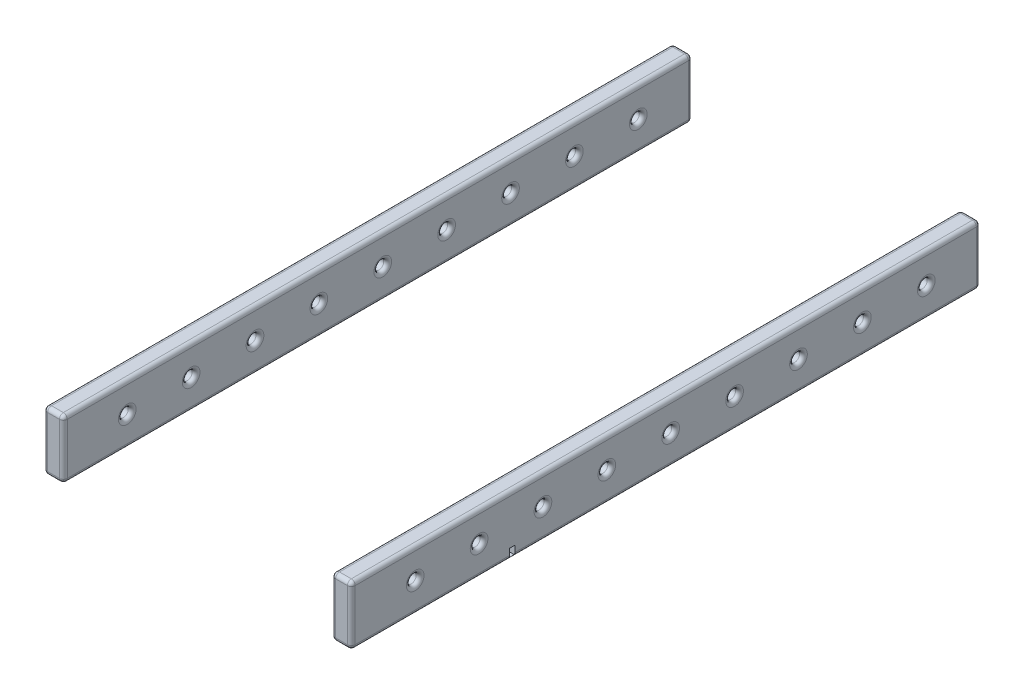
SolidWorks part; units mm, degrees
ref_plane "Front Plane" through (0, 0, 0) normal (0, 0, 1) x (1, 0, 0)
ref_plane "Top Plane" through (0, 0, 0) normal (0, 1, 0) x (1, 0, 0)
ref_plane "Right Plane" through (0, 0, 0) normal (1, 0, 0) x (0, 0, -1)
sketch "Sketch1" plane through (0, 0, 0) normal (0, 0, 1) x (1, 0, 0)
  line L0 (55, 0) -> (-55, 0) construction
  line L1 (-198.755, 38.1) -> (-173.355, 38.1)
  line L2 (-198.755, 38.1) -> (-198.755, -38.1)
  line L3 (-198.755, -38.1) -> (-173.355, -38.1)
  line L4 (-173.355, 38.1) -> (-173.355, -38.1)
  line L5 (-198.755, 38.1) -> (-173.355, -38.1) construction
  line L6 (-198.755, -38.1) -> (-173.355, 38.1) construction
  line L7 (0, -55) -> (0, 55) construction
  line L8 (198.755, -38.1) -> (173.355, -38.1)
  line L9 (173.355, 38.1) -> (173.355, -38.1)
  line L10 (198.755, 38.1) -> (173.355, 38.1)
  line L11 (198.755, 38.1) -> (198.755, -38.1)
  point P0 (-186.055, 0)
  dimension "D1" = 173.355
extrude "Boss-Extrude1" add sketch "Sketch1" along normal blind 406.4 and the other way blind 406.4
sketch "Sketch2" plane through (198.755, 0, 0) normal (1, 0, 0) x (0, 0, -1)
  line L0 (55, 0) -> (-55, 0) construction
  line L1 (-406.4, -38.1) -> (-406.4, 38.1) construction
  circle A0 centre (-323.85, 0) radius 6.35
  dimension "D1" = 82.55
extrude "Cut-Extrude1" cut sketch "Sketch2" against normal through all both and the other way through all
pattern_linear "LPattern1" count 9 spacing 82.55 along (0, 0, -1) of "Cut-Extrude1"
fillet "Fillet1" radius 5.08 30 edges at (186.055, -38.1, -406.4) (186.055, 38.1, -406.4) (173.355, 0, -406.4) (173.355, 38.1, 0) (173.355, -38.1, 0) (173.355, -6.35, 323.85) (173.355, -6.35, 241.3) (173.355, -6.35, 158.75) (173.355, -6.35, 76.2) (173.355, -6.35, -6.35) (173.355, -6.35, -88.9) (173.355, -6.35, -171.45) (173.355, -6.35, -254) (173.355, -6.35, -336.55) (186.055, -38.1, 406.4) (173.355, 0, 406.4) (186.055, 38.1, 406.4) (198.755, 0, -406.4) (198.755, -38.1, 0) (198.755, 0, 406.4) (198.755, 38.1, 0) (198.755, 6.35, 323.85) (198.755, 6.35, 241.3) (198.755, 6.35, 158.75) (198.755, 6.35, 76.2) (198.755, 6.35, -6.35) (198.755, 6.35, -88.9) (198.755, 6.35, -171.45) (198.755, 6.35, -254) (198.755, 6.35, -336.55)
fillet "Fillet2" radius 5.08 30 edges at (-186.055, -38.1, 406.4) (-186.055, -38.1, -406.4) (-198.755, 0, -406.4) (-198.755, 0, 406.4) (-198.755, -38.1, 0) (-198.755, 0, 317.5) (-198.755, 0, 234.95) (-198.755, 0, 152.4) (-198.755, 0, 69.85) (-198.755, 0, -12.7) (-198.755, 0, -95.25) (-198.755, 0, -177.8) (-198.755, 0, -260.35) (-198.755, 0, -342.9) (-186.055, 38.1, -406.4) (-186.055, 38.1, 406.4) (-198.755, 38.1, 0) (-173.355, 0, -406.4) (-173.355, -38.1, 0) (-173.355, 0, 406.4) (-173.355, 38.1, 0) (-173.355, 6.35, 323.85) (-173.355, 6.35, 241.3) (-173.355, 6.35, 158.75) (-173.355, 6.35, 76.2) (-173.355, 6.35, -6.35) (-173.355, 6.35, -88.9) (-173.355, 6.35, -171.45) (-173.355, 6.35, -254) (-173.355, 6.35, -336.55)
sketch "Sketch4" plane through (198.755, 0, 0) normal (1, 0, 0) x (0, 0, -1)
  line L0 (-406.4, -33.02) -> (-406.4, 33.02) construction
  line L1 (-201.93, -35.814) -> (-195.072, -35.814)
  line L2 (-201.93, -35.814) -> (-201.93, -24.892)
  line L3 (-201.93, -24.892) -> (-195.072, -24.892)
  line L4 (-195.072, -35.814) -> (-195.072, -24.892)
  line L5 (-201.93, -35.814) -> (-195.072, -24.892) construction
  line L6 (-201.93, -24.892) -> (-195.072, -35.814) construction
  line L7 (401.32, -38.1) -> (-401.32, -38.1) construction
  point P0 (-198.501, -30.353)
  point P7 (-201.93, -30.353)
  dimension "D1" = 204.47
  dimension "D2" = 2.286
extrude "Cut-Extrude2" cut sketch "Sketch4" against normal up to surface (372.11 mm away) up to face at (-173.355, 0, 0)
